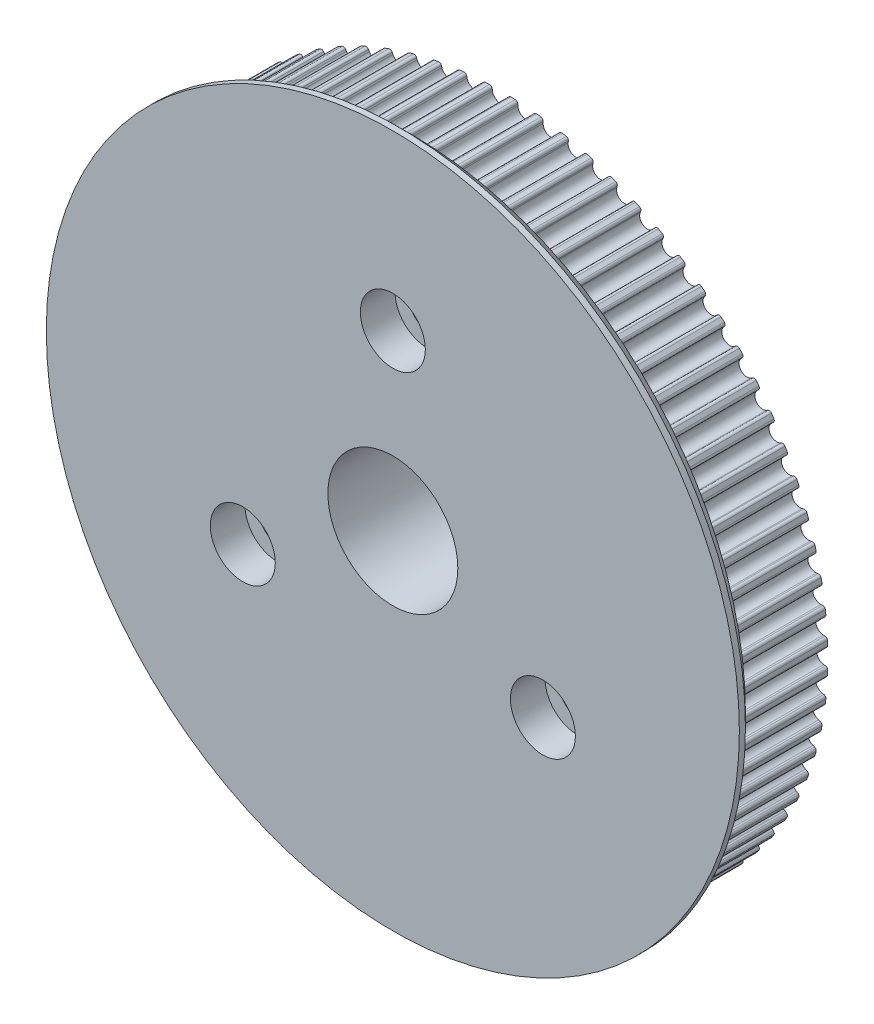
SolidWorks part; units mm, degrees
ref_plane "Front Plane" through (0, 0, 0) normal (0, 0, 1) x (1, 0, 0)
ref_plane "Top Plane" through (0, 0, 0) normal (0, 1, 0) x (1, 0, 0)
ref_plane "Right Plane" through (0, 0, 0) normal (1, 0, 0) x (0, 0, -1)
sketch "Sketch1" plane through (0, 0, 0) normal (0, 0, 1) x (1, 0, 0)
  circle A0 centre (0, 0) radius 37.815
  dimension "D1" = 75.63
extrude "Boss-Extrude1" add sketch "Sketch1" along normal blind 10.2
sketch "Sketch3" plane through (0, 0, 10.2) normal (0, 0, 1) x (1, 0, 0)
  line L0 (0, 37.815) -> (0, 0) construction
  line L1 (-0.9032, 37.3341) -> (-1.0564, 38.5817) construction
  line L2 (0.9032, 37.3341) -> (1.0576, 38.5912) construction
  line L3 (0, 0) -> (-1.4846, 37.7858) construction
  line L4 (0, 0) -> (1.4846, 37.7858) construction
  line L5 (-0.9275, 37.5315) -> (-0.9032, 37.3341)
  line L6 (0.9032, 37.3341) -> (0.9275, 37.5315)
  line L7 (-1.4846, 37.7858) -> (0, 42.815)
  line L8 (0, 42.815) -> (1.4846, 37.7858)
  circle A0 centre (0, 0) radius 37.815 construction
  arc A1 (-0.9032, 37.3341) -> (0.9032, 37.3341) centre (0, 37.445) ccw
  circle A2 centre (0, 0) radius 37.815 construction
  arc A3 (-0.9275, 37.5315) -> (-1.235, 37.7948) centre (-1.2252, 37.495) ccw
  arc A4 (0.9275, 37.5315) -> (1.235, 37.7948) centre (1.2252, 37.495) cw
  arc A5 (1.235, 37.7948) -> (1.4846, 37.7858) centre (0, 0) cw
  arc A6 (-1.235, 37.7948) -> (-1.4846, 37.7858) centre (0, 0) ccw
  dimension "D2" = 0.37
  dimension "D1" = 0.91
  dimension "D3" = 14
  dimension "D4" = 0.3
  dimension "D7" = 0.3
  dimension "D5" = 4.5
  dimension "D6" = 2.25
  dimension "D8" = 5
extrude "Cut-Extrude1" cut sketch "Sketch3" against normal up to surface (10.2 mm away) up to face at (37.815, 0, 0)
pattern_circular "CirPattern1" count 80 over 360 about axis through (0, 0, 10.2) along (0, 0, 1) of "Cut-Extrude1"
sketch "Sketch4" plane through (0, 0, 10.2) normal (0, 0, 1) x (1, 0, 0)
  circle A0 centre (0, 0) radius 40
  dimension "D1" = 80
extrude "Boss-Extrude2" add sketch "Sketch4" along normal blind 2.2
sketch "Sketch5" plane through (0, 0, 12.4) normal (0, 0, 1) x (1, 0, 0)
  circle A0 centre (0, 0) radius 7.5
  dimension "D1" = 15
extrude "Cut-Extrude2" cut sketch "Sketch5" against normal up to surface (12.4 mm away) up to face at (0, 0, 0)
chamfer "Chamfer1" distance 1.5 angle 45 1 edges at (40, 0, 10.2)
sketch "Sketch8" plane through (0, 0, 12.4) normal (0, 0, 1) x (1, 0, 0)
  line L1 (0, 0) -> (0, 20) construction
  circle A0 centre (0, 20) radius 2
  circle A7 centre (17.3205, -10) radius 2
  circle A8 centre (-17.3205, -10) radius 2
  point P9 (0, 0)
  point P15 (0, 0)
  dimension "D3" = 4
  dimension "D1" = 3
  dimension "D2" = 20
extrude "Cut-Extrude6" cut sketch "Sketch8" against normal up to surface (12.4 mm away) up to face at (7.5, 0, 0)
sketch "Sketch9" plane through (0, 0, 12.4) normal (0, 0, 1) x (1, 0, 0)
  circle A0 centre (0, 20) radius 3.75
  circle A1 centre (17.3205, -10) radius 3.75
  circle A2 centre (-17.3205, -10) radius 3.75
  dimension "D2" = 7.5
  dimension "D3" = 7.5
  dimension "D4" = 7.5
extrude "Cut-Extrude5" cut sketch "Sketch9" against normal blind 4
